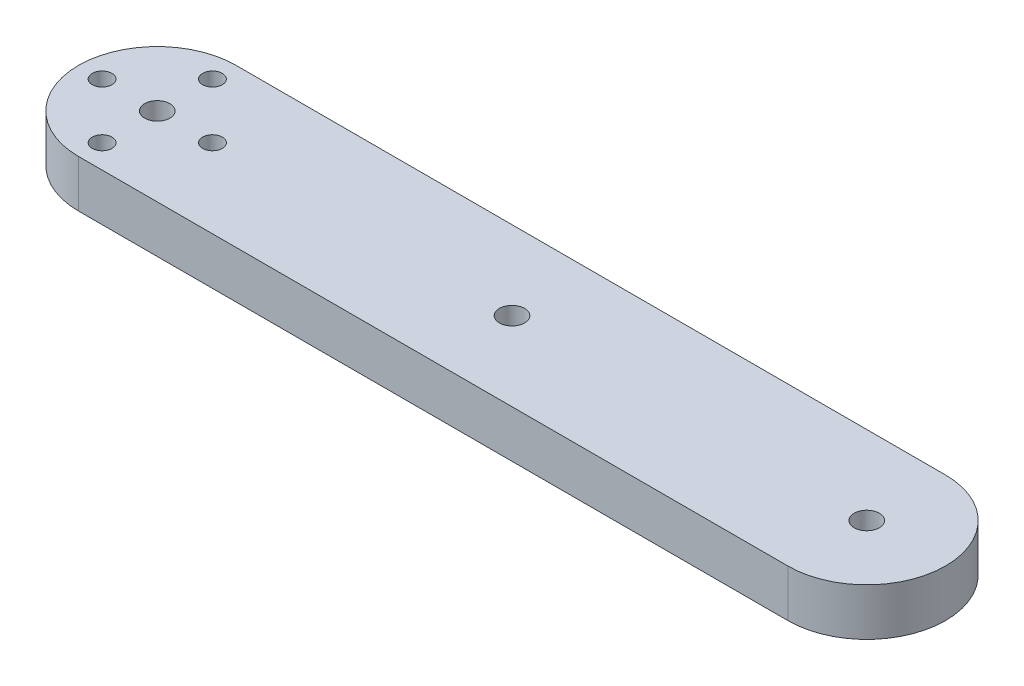
SolidWorks part; units mm, degrees
ref_plane "Front Plane" through (0, 0, 0) normal (0, 0, 1) x (1, 0, 0)
ref_plane "Top Plane" through (0, 0, 0) normal (0, 1, 0) x (1, 0, 0)
ref_plane "Right Plane" through (0, 0, 0) normal (1, 0, 0) x (0, 0, -1)
sketch "Sketch1" plane through (0, 0, 0) normal (0, 1, 0) x (1, 0, 0)
  line L0 (-45, 20) -> (-45, 0) construction
  line L1 (0, 0) -> (-90, 0)
  line L3 (0, 20) -> (-90, 20)
  line L5 (-90, 20) -> (-90, 0) construction
  line L6 (-100, 10) -> (-80, 10) construction
  line L7 (10, 10) -> (8.25, 10) construction
  line L8 (0, 20) -> (0, 18.25) construction
  line L9 (-8.25, 10) -> (-10, 10) construction
  line L10 (0, 15.75) -> (0, 4.25) construction
  line L11 (1.6, 10) -> (-5.75, 10) construction
  line L12 (0, 1.75) -> (0, 0) construction
  arc A0 (-90, 20) -> (-90, 0) centre (-90, 10) ccw
  arc A1 (0, 20) -> (0, 0) centre (0, 10) cw
  circle A2 centre (-90, 10) radius 1.6
  circle A3 centre (-90, 10) radius 10 construction
  circle A4 centre (0, 10) radius 10 construction
  circle A5 centre (-90, 17) radius 1.25
  circle A6 centre (-90, 3) radius 1.25
  circle A7 centre (-97, 10) radius 1.25
  circle A8 centre (-83, 10) radius 1.25
  circle A10 centre (0, 10) radius 1.6
  circle A14 centre (-45, 10) radius 1.6
  dimension "D3" = 20
  dimension "D4" = 3.2
  dimension "D5" = 2.5
  dimension "D7" = 2.5
  dimension "D9" = 3.2
  dimension "D1" = 90
  dimension "D2" = 20
  dimension "D6" = 7
  dimension "D8" = 7
extrude "Boss-Extrude1" add sketch "Sketch1" along normal blind 6
